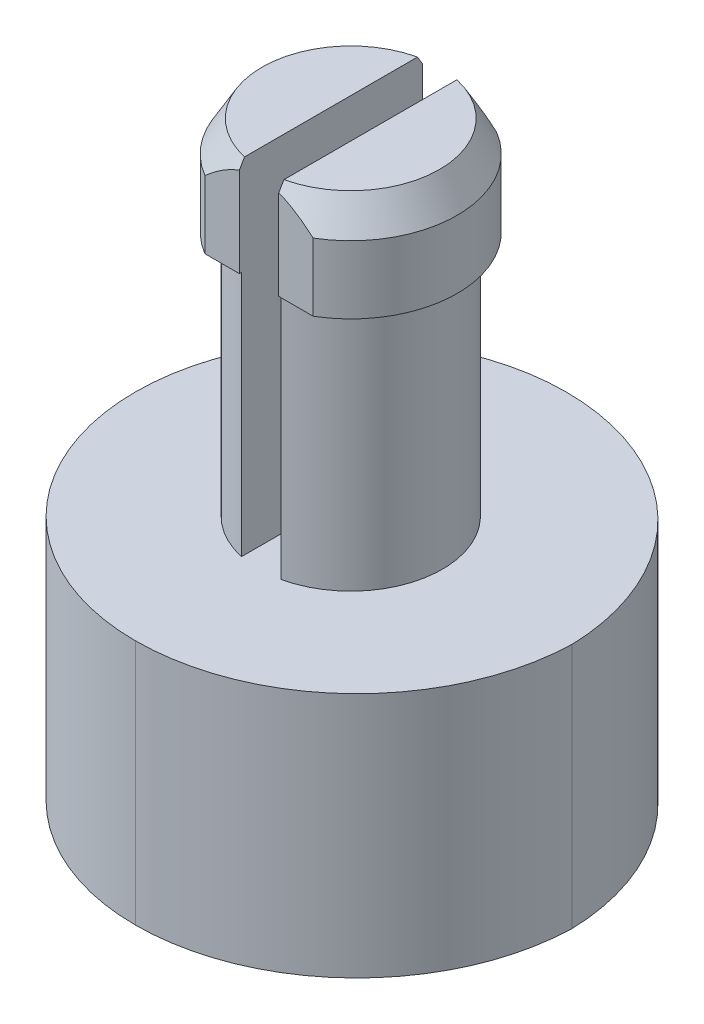
SolidWorks part; units mm, degrees
ref_plane "Front Plane" through (0, 0, 0) normal (0, 0, 1) x (1, 0, 0)
ref_plane "Top Plane" through (0, 0, 0) normal (0, 1, 0) x (1, 0, 0)
ref_plane "Right Plane" through (0, 0, 0) normal (1, 0, 0) x (0, 0, -1)
sketch "Sketch1" plane through (0, 0, 0) normal (0, 0, 1) x (1, 0, 0)
  line L0 (3.302, 0) -> (15.367, 0)
  line L1 (-6.477, 0) -> (-3.302, 0)
  line L2 (-6.477, 0) -> (-6.477, -6.35)
  line L3 (-6.477, -6.35) -> (15.367, -6.35)
  line L4 (15.367, 0) -> (15.367, -6.35)
  arc A0 (-3.302, 0) -> (3.302, 0) centre (0, 0) ccw
  dimension "D1" = 3.302
  dimension "D2" = 3.175
  dimension "D3" = 6.35
  dimension "D4" = 21.844
extrude "Boss-Extrude1" add sketch "Sketch1" along normal blind 11.1125 contours L2 L3 L4 L0 A0 L1
fillet "Fillet1" radius 6.35 1 edges at (-6.477, -6.35, 5.5562)
fillet "Fillet2" radius 5.715 2 edges at (15.367, -3.175, 0) (15.367, -3.175, 11.1125)
sketch "Sketch2" plane through (0, 0, 0) normal (0, 1, 0) x (1, 0, 0)
  circle A0 centre (9.652, -5.5562) radius 2.365
  dimension "D1" = 4.73
extrude "Boss-Extrude2" add sketch "Sketch2" along normal blind 6.35
sketch "Sketch3" plane through (0, 6.35, 0) normal (0, 1, 0) x (1, 0, 0)
  line L4 (8.2565, -7.9212) -> (11.0475, -7.9212)
  line L8 (8.2565, -3.1913) -> (11.0475, -3.1912)
  arc A0 (11.0475, -7.9212) -> (11.0475, -3.1912) centre (9.652, -5.5562) ccw
  circle A1 centre (9.652, -5.5562) radius 2.365 construction
  circle A2 centre (9.652, -5.5562) radius 2.365 construction
  arc A3 (8.2565, -3.1913) -> (8.2565, -7.9212) centre (9.652, -5.5562) ccw
  dimension "D1" = 5.492
extrude "Boss-Extrude3" add sketch "Sketch3" along normal blind 2.54
sketch "Sketch4" plane through (0, 0, 0) normal (0, 0, 1) x (1, 0, 0)
  line L0 (12.398, 8.89) -> (11.0475, 8.89) construction
  line L1 (9.144, 8.89) -> (10.16, 8.89)
  line L2 (9.144, 8.89) -> (9.144, 0)
  line L3 (9.144, 0) -> (10.16, 0)
  line L4 (10.16, 8.89) -> (10.16, 0)
  line L6 (9.652, 8.89) -> (9.652, 0) construction
  line L7 (9.652, -6.35) -> (9.652, 0) construction
  line L8 (12.017, 0) -> (7.287, 0) construction
  dimension "D1" = 1.016
extrude "Cut-Extrude2" cut sketch "Sketch4" along normal through all
chamfer "Chamfer1" distance 0.7937 angle 30 2 edges at (6.906, 8.89, 5.5562) (12.398, 8.89, 5.5562) first distance on face at (7.5813, 7.62, 5.5562) first distance on face at (11.7227, 7.62, 5.5562)
sketch "Sketch5" plane through (0, 0, 0) normal (0, 1, 0) x (1, 0, 0)
  line L0 (9.652, 0) -> (-6.477, 0)
  line L1 (-6.477, 0) -> (-6.477, -11.1125)
  line L2 (-6.477, -11.1125) -> (9.652, -11.1125)
  arc A0 (9.652, 0) -> (9.652, -11.1125) centre (9.652, -5.5562) ccw
extrude "Cut-Extrude3" cut sketch "Sketch5" against normal through all
